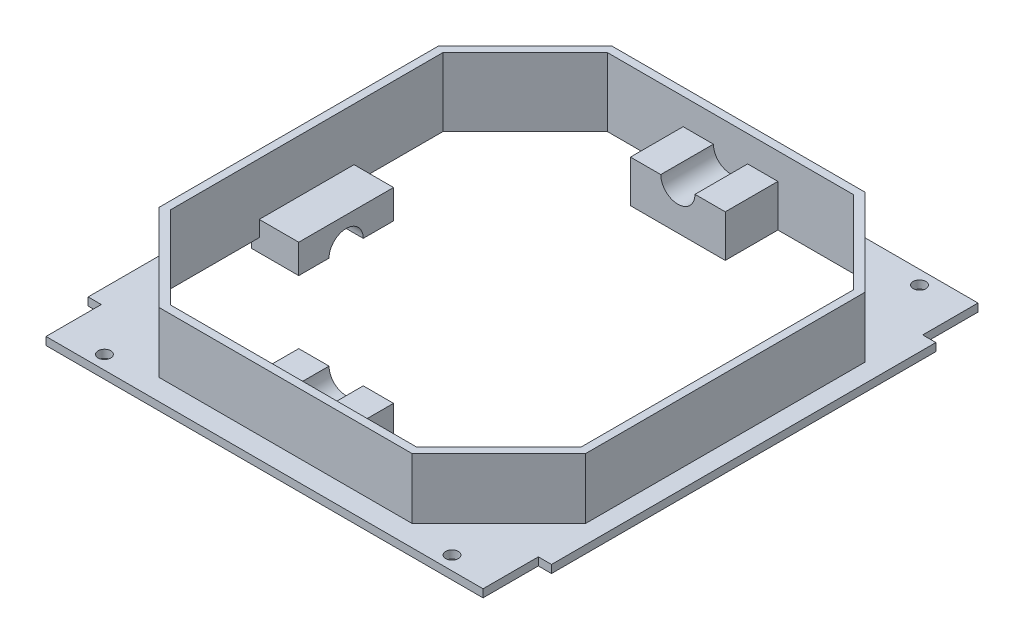
SolidWorks part; units mm, degrees
ref_plane "Front Plane" through (0, 0, 0) normal (0, 0, 1) x (1, 0, 0)
ref_plane "Top Plane" through (0, 0, 0) normal (0, 1, 0) x (1, 0, 0)
ref_plane "Right Plane" through (0, 0, 0) normal (1, 0, 0) x (0, 0, -1)
sketch "Sketch1" plane through (0, 0, 0) normal (0, 1, 0) x (1, 0, 0)
  line L5 (-44, -46.5) -> (44, -46.5)
  line L6 (-44, -46.5) -> (-44, 46.5)
  line L7 (-44, 46.5) -> (44, 46.5)
  line L8 (44, -46.5) -> (44, 46.5)
  line L9 (-44, -46.5) -> (44, 46.5) construction
  line L10 (-44, 46.5) -> (44, -46.5) construction
  point P0 (0, 0)
  dimension "D1" = 88
  dimension "D2" = 93
extrude "Boss-Extrude1" add sketch "Sketch1" along normal blind 13
sketch "Sketch2" plane through (0, 13, 0) normal (0, 1, 0) x (1, 0, 0)
  line L0 (0, 46.5) -> (0, -46.5) construction
  line L1 (-44, -46.5) -> (44, -46.5) construction
  line L2 (-44, 0) -> (44, 0) construction
  line L3 (44, -46.5) -> (44, 46.5) construction
  line L4 (-24, -43) -> (-40.5, -26.5)
  line L5 (-44, 46.5) -> (-44, -46.5) construction
  line L6 (-44, -36.5) -> (-44, -46.5)
  line L7 (-44, -46.5) -> (-34, -46.5)
  line L11 (-24, -43) -> (24, -43)
  line L14 (-34, -46.5) -> (34, -46.5)
  line L15 (-40.5, -26.5) -> (-40.5, 26.5)
  line L17 (-44, -36.5) -> (-44, 36.5)
  line L18 (44, -36.5) -> (44, 36.5)
  line L19 (40.5, -26.5) -> (40.5, 26.5)
  line L20 (44, -46.5) -> (34, -46.5)
  line L21 (44, -36.5) -> (44, -46.5)
  line L22 (24, -43) -> (40.5, -26.5)
  line L23 (24, 43) -> (40.5, 26.5)
  line L24 (44, 36.5) -> (44, 46.5)
  line L25 (44, 46.5) -> (34, 46.5)
  line L26 (-34, 46.5) -> (34, 46.5)
  line L27 (-24, 43) -> (24, 43)
  line L28 (-44, 46.5) -> (-34, 46.5)
  line L29 (-44, 36.5) -> (-44, 46.5)
  line L30 (-24, 43) -> (-40.5, 26.5)
  point P6 (0, 0)
  point P12 (0, 0)
  point P29 (0, -43)
  point P35 (40.5, 0)
  point P37 (-40.5, 0)
  point P40 (0, 43)
  dimension "D1" = 45
  dimension "D2" = 10
  dimension "D3" = 10
  dimension "D4" = 3.5
  dimension "D5" = 3.5
  dimension "D6" = 20
extrude "Cut-Extrude1" cut sketch "Sketch2" against normal offset from surface (11.5 mm away) 1.5 up to face at (0, 0, 0)
sketch "Sketch3" plane through (0, 13, 0) normal (0, 1, 0) x (1, 0, 0)
  line L16 (-23.3787, -41.5) -> (23.3787, -41.5)
  line L17 (23.3787, -41.5) -> (39, -25.8787)
  line L18 (39, -25.8787) -> (39, 25.8787)
  line L19 (39, 25.8787) -> (23.3787, 41.5)
  line L20 (23.3787, 41.5) -> (-23.3787, 41.5)
  line L21 (-23.3787, 41.5) -> (-39, 25.8787)
  line L22 (-39, 25.8787) -> (-39, -25.8787)
  line L23 (-39, -25.8787) -> (-23.3787, -41.5)
  line L24 (-23.3787, -41.5) -> (23.3787, -41.5)
  line L25 (23.3787, -41.5) -> (39, -25.8787)
  line L26 (39, -25.8787) -> (39, 25.8787)
  line L27 (39, 25.8787) -> (23.3787, 41.5)
  line L28 (23.3787, 41.5) -> (-23.3787, 41.5)
  line L29 (-23.3787, 41.5) -> (-39, 25.8787)
  line L30 (-39, 25.8787) -> (-39, -25.8787)
  line L31 (-39, -25.8787) -> (-23.3787, -41.5)
  dimension "D1" = 1.5
extrude "Cut-Extrude2" cut sketch "Sketch3" against normal through all
sketch "Sketch4" plane through (0, 0, -41.5) normal (0, 0, 1) x (1, 0, 0)
  line L0 (0, 0) -> (0, 8) construction
  line L1 (23.3787, 0) -> (-23.3787, 0) construction
  line L2 (3.25, 8) -> (9, 8)
  line L3 (9, 8) -> (9, 0)
  line L4 (-9, 0) -> (9, 0)
  line L5 (3.25, 8) -> (-3.25, 8) construction
  line L6 (-9, 8) -> (-9, 0)
  line L7 (-3.25, 8) -> (-9, 8)
  arc A0 (-3.25, 8) -> (3.25, 8) centre (0, 8) ccw
  dimension "D1" = 3.25
  dimension "D2" = 8
  dimension "D3" = 18
extrude "Boss-Extrude2" add sketch "Sketch4" along normal blind 10
sketch "Sketch5" plane through (39, 0, 0) normal (-1, 0, 0) x (0, 0, 1)
  line L0 (0, 0) -> (0, -2.5) construction
  line L2 (25.8787, 0) -> (-25.8787, 0) construction
  line L3 (3.25, -2.5) -> (9, -2.5)
  line L4 (9, -2.5) -> (9, 3)
  line L6 (-9, -2.5) -> (-9, 3)
  line L7 (-3.25, -2.5) -> (-9, -2.5)
  line L8 (-9, 3) -> (9, 3)
  arc A1 (3.25, -2.5) -> (-3.25, -2.5) centre (0, -2.5) ccw
  dimension "D2" = 2.5
  dimension "D1" = 6.5
  dimension "D3" = 18
  dimension "D4" = 5.5
extrude "Boss-Extrude3" add sketch "Sketch5" along normal blind 7.5 and the other way up to surface (1.5 mm away) other way up to face at (40.5, 7.25, 0)
extrude "Boss-Extrude4" add sketch "Sketch5<2>" against normal blind 7.5 and the other way up to surface (79.5 mm away) from surface other way up to face at (-40.5, 7.25, 0) starting at face at (-39, 6.5, 0)
sketch "Sketch5<2>" plane through (39, 0, 0) normal (-1, 0, 0) x (0, 0, 1) same geometry as "Sketch5"
extrude "Boss-Extrude5" add sketch "Sketch4<2>" against normal blind 10 from surface starting at face at (0, 6.5, 41.5)
sketch "Sketch4<2>" plane through (0, 0, -41.5) normal (0, 0, 1) x (1, 0, 0) same geometry as "Sketch4"
sketch "Sketch6" plane through (0, 1.5, 0) normal (0, 1, 0) x (1, 0, 0)
  line L0 (-44, 0) -> (44, 0) construction
  line L1 (44, -46.5) -> (41.5, -46.5)
  line L2 (44, -46.5) -> (44, -36.5)
  line L3 (44, -36.5) -> (41.5, -36.5)
  line L4 (41.5, -46.5) -> (41.5, -36.5)
  line L5 (44, -46.5) -> (44, 46.5) construction
  line L6 (0, -46.5) -> (0, 46.5) construction
  line L7 (44, 46.5) -> (-44, 46.5) construction
  line L8 (41.5, 46.5) -> (41.5, 36.5)
  line L9 (44, 36.5) -> (41.5, 36.5)
  line L10 (44, 46.5) -> (44, 36.5)
  line L11 (44, 46.5) -> (41.5, 46.5)
  line L12 (-44, 46.5) -> (-41.5, 46.5)
  line L13 (-44, 46.5) -> (-44, 36.5)
  line L14 (-44, 36.5) -> (-41.5, 36.5)
  line L15 (-41.5, 46.5) -> (-41.5, 36.5)
  line L16 (-41.5, -46.5) -> (-41.5, -36.5)
  line L17 (-44, -36.5) -> (-41.5, -36.5)
  line L18 (-44, -46.5) -> (-44, -36.5)
  line L19 (-44, -46.5) -> (-41.5, -46.5)
  point P12 (0, 0)
  point P17 (0, 0)
  dimension "D1" = 2.5
  dimension "D2" = 10
extrude "Cut-Extrude3" cut sketch "Sketch6" against normal through all
sketch "Sketch8" plane through (0, 0, -46.5) normal (0, 0, -1) x (-1, 0, 0)
  line L4 (-41.5, 0) -> (41.5, 0)
  line L5 (41.5, 0) -> (41.5, 1.5)
  line L6 (41.5, 1.5) -> (-41.5, 1.5)
  line L7 (-41.5, 1.5) -> (-41.5, 0)
  line L8 (-41.5, 0) -> (41.5, 0)
  line L9 (41.5, 0) -> (41.5, 1.5)
  line L10 (41.5, 1.5) -> (-41.5, 1.5)
  line L11 (-41.5, 1.5) -> (-41.5, 0)
  dimension "D1" = 0
extrude "Boss-Extrude6" add sketch "Sketch8" along normal blind 0.5
mirror "Mirror1" about plane through (0, 0, 0) normal (0, 0, 1) of "Boss-Extrude6"
sketch "Sketch9" plane through (0, 0, 0) normal (0, 1, 0) x (1, 0, 0)
  line L0 (41.5, -36.5) -> (41.5, -47) construction
  line L1 (-41.5, -47) -> (41.5, -47) construction
  line L2 (-44, 0) -> (44, 0) construction
  line L3 (44, -36.5) -> (44, 36.5) construction
  line L4 (0, -47) -> (0, 47) construction
  line L5 (-41.5, 47) -> (41.5, 47) construction
  circle A0 centre (33, -44.4) radius 1.2
  circle A1 centre (33, 44.4) radius 1.2
  circle A2 centre (-33, 44.4) radius 1.2
  circle A3 centre (-33, -44.4) radius 1.2
  point P12 (0, 0)
  point P18 (0, 0)
  dimension "D1" = 8.5
  dimension "D2" = 2.6
  dimension "D3" = 2.4
extrude "Cut-Extrude4" cut sketch "Sketch9" along normal through all
